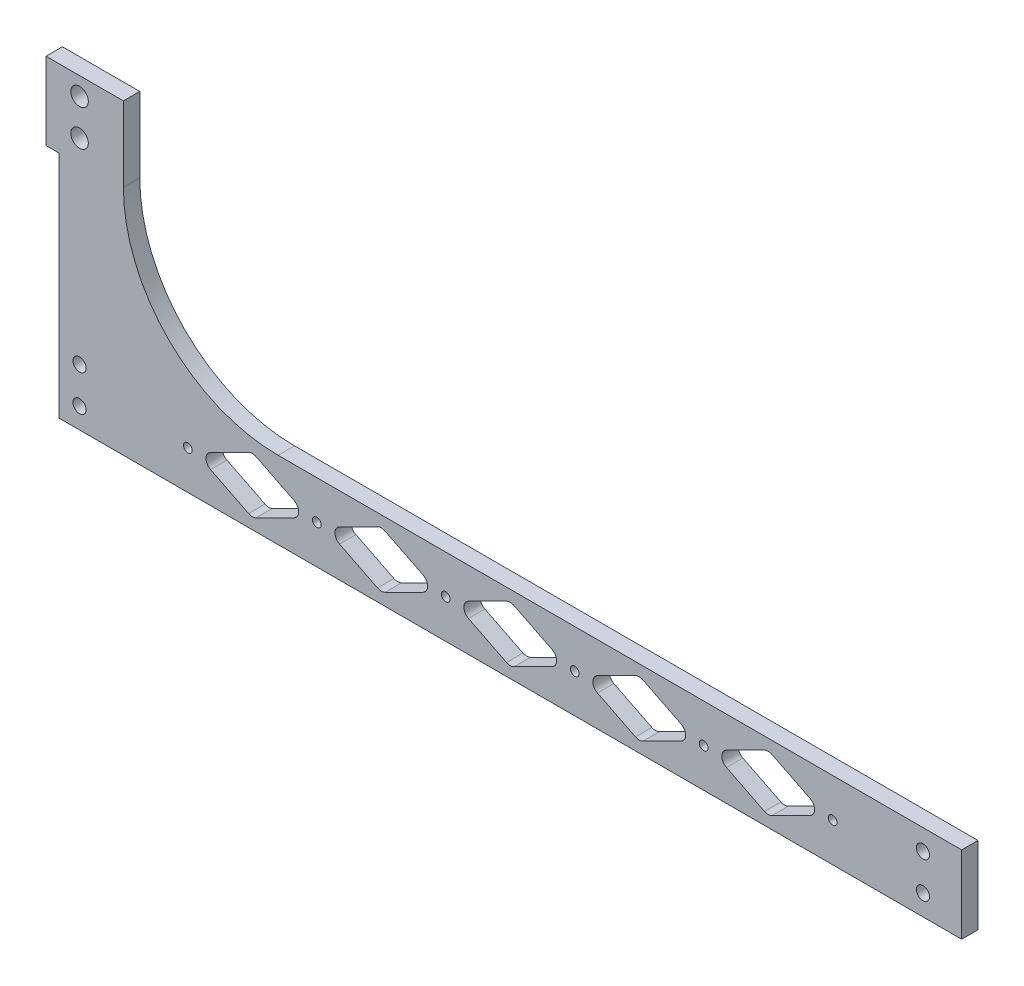
SolidWorks part; units mm, degrees
ref_plane "Front Plane" through (0, 0, 0) normal (0, 0, 1) x (1, 0, 0)
ref_plane "Top Plane" through (0, 0, 0) normal (0, 1, 0) x (1, 0, 0)
ref_plane "Right Plane" through (0, 0, 0) normal (1, 0, 0) x (0, 0, -1)
sketch "Sketch2" plane through (0, 0, 0) normal (0, 0, 1) x (1, 0, 0)
  line L1 (0, 0) -> (350, 0)
  line L2 (0, 0) -> (0, 30)
  line L3 (0, 30) -> (350, 30)
  line L4 (350, 0) -> (350, 30)
  dimension "D1" = 30
  dimension "D2" = 350
extrude "Boss-Extrude1" add sketch "Sketch2" along normal blind 6.35
sketch "Sketch3" plane through (0, 0, 6.35) normal (0, 0, 1) x (1, 0, 0)
  line L0 (8, 30) -> (8, 0) construction
  line L1 (350, 30) -> (0, 30) construction
  line L2 (0, 30) -> (0, 0) construction
  line L3 (0, 0) -> (350, 0) construction
  point P4 (8, 22)
  point P5 (8, 8)
  dimension "D1" = 8
  dimension "D2" = 8
  dimension "D3" = 8
hole_wizard "Tap Drill for 1/4-20 Tap2" positions "Sketch4" profile "Sketch5" hole size "1/4-20" standard "ANSI Inch" end condition through all
sketch "Sketch4" plane through (0, 0, 6.35) normal (0, 0, 1) x (1, 0, 0)
  point P0 (8, 22)
  point P3 (8, 8)
sketch "Sketch5" plane through (8, 22, 6.35) normal (1, 0, 0) x (0, -1, 0)
  line L0 (0, 0) -> (0, 6.35)
  line L1 (0, 6.35) -> (2.5527, 6.35)
  line L2 (2.5527, 6.35) -> (2.5527, 0)
  line L5 (2.5527, 0) -> (0, 0)
  line L11 (0, -6.35) -> (0, 107.95) construction
  dimension "Thru Hole Dia." = 5.1054
  dimension "Thru Hole Depth" = 6.35
sketch "Sketch6" plane through (0, 0, 6.35) normal (0, 0, 1) x (1, 0, 0)
  line L0 (0, 15) -> (350, 15) construction
  line L1 (0, 30) -> (0, 0) construction
  line L2 (350, 0) -> (350, 30) construction
  point P6 (50, 15)
  dimension "D1" = 50
hole_wizard "M3 Clearance Hole1" positions "Sketch6" profile "Sketch7" hole size "M3" standard "ANSI Metric" end condition through all
sketch "Sketch7" plane through (50, 15, 6.35) normal (1, 0, 0) x (0, -1, 0)
  line L0 (0, 0) -> (0, 6.35)
  line L1 (0, 6.35) -> (1.7, 6.35)
  line L2 (1.7, 6.35) -> (1.7, 0)
  line L5 (1.7, 0) -> (0, 0)
  line L11 (0, -6.35) -> (0, 107.95) construction
  dimension "Thru Hole Dia." = 3.4
  dimension "Thru Hole Depth" = 6.35
pattern_linear "LPattern1" count 6 spacing 50 along (1, 0, 0) of "M3 Clearance Hole1"
sketch "Sketch8" plane through (0, 0, 0) normal (0, 0, -1) x (-1, 0, 0)
  line L0 (-335, 30) -> (-335, 0) construction
  line L1 (-350, 30) -> (0, 30) construction
  line L2 (0, 0) -> (-350, 0) construction
  line L3 (-350, 0) -> (-350, 30) construction
  point P6 (-335, 15)
  point P7 (-335, 22)
  point P8 (-335, 8)
  dimension "D1" = 15
  dimension "D2" = 7
  dimension "D3" = 7
hole_wizard "Tap Drill for 1/4-20 Tap1" positions "Sketch11" profile "Sketch12" hole size "1/4-20" standard "ANSI Inch" end condition through all
sketch "Sketch11" plane through (0, 0, 0) normal (0, 0, -1) x (-1, 0, 0)
  point P0 (-335, 22)
  point P3 (-335, 8)
sketch "Sketch12" plane through (335, 22, 0) normal (1, 0, 0) x (0, 1, 0)
  line L0 (0, 0) -> (0, 6.35)
  line L1 (0, 6.35) -> (2.5527, 6.35)
  line L2 (2.5527, 6.35) -> (2.5527, 0)
  line L5 (2.5527, 0) -> (0, 0)
  line L11 (0, -6.35) -> (0, 107.95) construction
  dimension "Thru Hole Dia." = 5.1054
  dimension "Thru Hole Depth" = 6.35
sketch "Sketch13" plane through (0, 0, 0) normal (0, 0, -1) x (-1, 0, 0)
  line L0 (-100, 15) -> (-50, 15) construction
  line L1 (-75, 4) -> (-75, 26)
  line L2 (-75, 26) -> (-97, 15)
  line L3 (-97, 15) -> (-75, 4)
  line L4 (-75, 26) -> (-53, 15)
  line L5 (-53, 15) -> (-75, 4)
  point P7 (-75, 15)
  dimension "D1" = 22
  dimension "D2" = 22
extrude "Cut-Extrude1" cut sketch "Sketch13" against normal through all contours L0 L3 L1 | L2 L0 L1 | L1 L0 L4 | L0 L1 L5 region at (82.3333, 18.6667, 0) region at (82.3333, 11.3333, 0) region at (67.6667, 18.6667, 0) region at (67.6667, 11.3333, 0)
fillet "Fillet1" radius 3.25 4 edges at (53, 15, 3.175) (75, 4, 3.175) (97, 15, 3.175) (75, 26, 3.175)
pattern_linear "LPattern2" count 5 spacing 50 along (1, 0, 0) of "Cut-Extrude1", "Fillet1"
sketch "Sketch14" plane through (0, 0, 0) normal (0, 0, -1) x (-1, 0, 0)
  line L1 (0, 30) -> (-25, 30)
  line L2 (0, 30) -> (0, 119)
  line L3 (0, 119) -> (-25, 119)
  line L4 (-25, 30) -> (-25, 119)
  line L5 (0, 119) -> (5, 119)
  line L6 (0, 119) -> (0, 89)
  line L7 (0, 89) -> (5, 89)
  line L8 (5, 119) -> (5, 89)
  circle A0 centre (-8, 112) radius 3.4
  circle A1 centre (-8, 98) radius 3.4
  circle A4 centre (-8, 22) radius 2.5527 construction
  circle A5 centre (-8, 22) radius 2.5527 construction
  dimension "D1" = 6.8
  dimension "D2" = 14
  dimension "D3" = 7
  dimension "D4" = 90
  dimension "D5" = 25
  dimension "D6" = 30
  dimension "D7" = 5
extrude "Boss-Extrude2" add sketch "Sketch14" against normal up to surface (6.35 mm away) contours L4 L1 L2 L3 A1 A0 | L8 L5 L2 L7 region at (12.6519, 73.4707, 0) region at (-2.5, 104, 0) up to face at (75, 15, 6.35)
fillet "Fillet2" radius 60 1 edges at (25, 30, 3.175)
